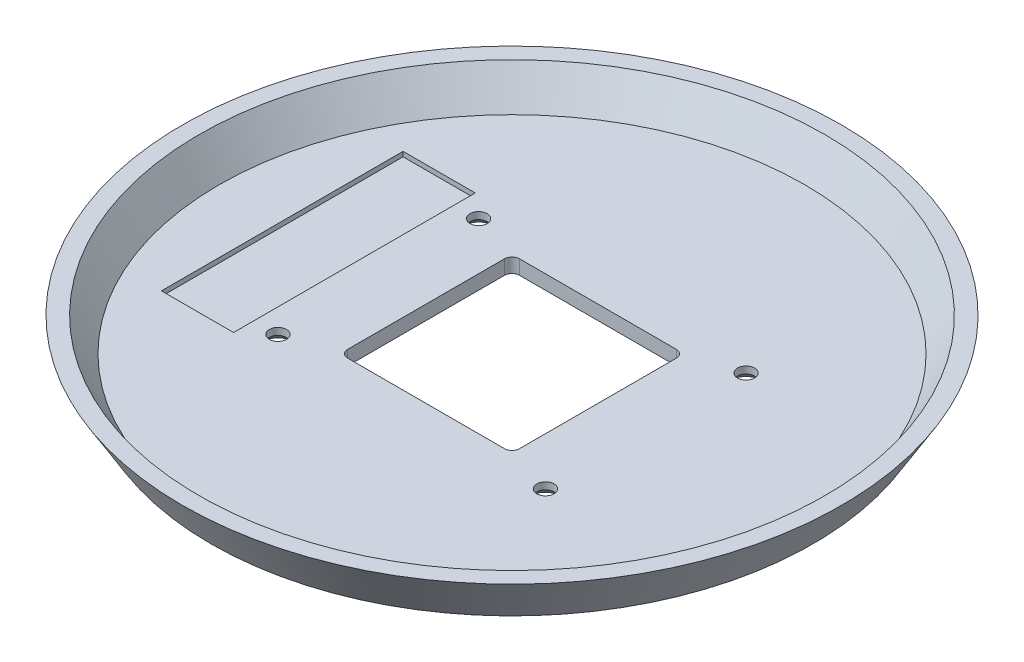
SolidWorks part; units mm, degrees
ref_plane "Front Plane" through (0, 0, 0) normal (0, 0, 1) x (1, 0, 0)
ref_plane "Top Plane" through (0, 0, 0) normal (0, 1, 0) x (1, 0, 0)
ref_plane "Right Plane" through (0, 0, 0) normal (1, 0, 0) x (0, 0, -1)
sketch "Sketch1" plane through (0, 0, 0) normal (0, 0, 1) x (1, 0, 0)
  line L0 (0, 0) -> (63, 0)
  line L1 (63, 0) -> (69, 10)
  line L6 (0, 3) -> (61.3014, 3)
  line L7 (61.3014, 3) -> (65.5014, 10)
  line L8 (69, 10) -> (65.5014, 10)
  line L9 (0, 0) -> (0, 3)
  line L10 (61.3014, 3) -> (66.4275, 11.5435) construction
  dimension "D1" = 69
  dimension "D2" = 63
  dimension "D3" = 10
  dimension "D4" = 3
revolve "Revolve1" add sketch "Sketch1" angle 360 about L9
sketch "Sketch2" plane through (0, 3, 0) normal (0, 1, 0) x (1, 0, 0)
  line L1 (-18, 18) -> (18, 18)
  line L2 (-18, 18) -> (-18, -18)
  line L3 (-18, -18) -> (18, -18)
  line L4 (18, 18) -> (18, -18)
  line L5 (-18, 18) -> (18, -18) construction
  line L6 (-18, -18) -> (18, 18) construction
  point P0 (0, 0)
  dimension "D1" = 36
  dimension "D2" = 36
  dimension "D12" = 0
  dimension "D13" = 0
extrude "Cut-Extrude1" cut sketch "Sketch2" against normal through all
fillet "Fillet1" radius 1.6 4 edges at (18, 1.5, -18) (18, 1.5, 18) (-18, 1.5, 18) (-18, 1.5, -18)
hole_wizard "CSK for M3 Countersunk Flat Head Screw2" positions "3DSketch3" profile "Sketch6" countersink size "M3" standard "ISO" end condition up to next
sketch3d "3DSketch3"
  line L0 (16.4, 0, -18) -> (-16.4, 0, -18) construction
  line L1 (-16.4, 0, 18) -> (16.4, 0, 18) construction
  line L2 (18, 0, 16.4) -> (18, 0, -16.4) construction
  line L3 (-18, 0, -16.4) -> (-18, 0, 16.4) construction
  point P0 (-28, 0, -21)
  point P2 (-28, 0, 21)
  point P4 (28, 0, 21)
  point P6 (28, 0, -21)
  dimension "D1" = 3
  dimension "D2" = 3
  dimension "D3" = 3
  dimension "D4" = 3
  dimension "D5" = 10
  dimension "D6" = 10
  dimension "D7" = 10
  dimension "D8" = 10
sketch "Sketch6" plane through (-28, 0, -21) normal (1, 0, 0) x (0, 0, -1)
  line L0 (0, 0) -> (0, 3)
  line L1 (0, 3) -> (1.8, 3)
  line L2 (1.8, 3) -> (1.8, 1.55)
  line L3 (1.8, 1.55) -> (3.35, 0)
  line L5 (3.35, 0) -> (0, 0)
  line L6 (-1.8, 1.55) -> (-3.35, 0) construction
  line L11 (0, -6.35) -> (0, 107.95) construction
  dimension "Thru Hole Dia." = 3.6
  dimension "Thru Hole Depth" = 3
  dimension "Near C'Sink Dia." = 6.7
  dimension "Near C'Sink Angle" = 90
sketch "Sketch19" plane through (0, 3, 0) normal (0, 1, 0) x (1, 0, 0)
  line L0 (-33, 25) -> (-33, -25) construction
  line L1 (-48.1, 25.3) -> (-33, 25.3)
  line L2 (-48.1, 25.3) -> (-48.1, -25.3)
  line L3 (-48.1, -25.3) -> (-33, -25.3)
  line L4 (-33, 25.3) -> (-33, -25.3)
  line L5 (-47.8, 25) -> (-47.8, -25) construction
  line L6 (67.7, 25) -> (-47.8, 25) construction
  line L7 (67.7, -25) -> (-47.8, -25) construction
  dimension "D1" = 0.3
  dimension "D2" = 0.3
  dimension "D3" = 0.3
extrude "Cut-Extrude4" cut sketch "Sketch19" against normal blind 1
